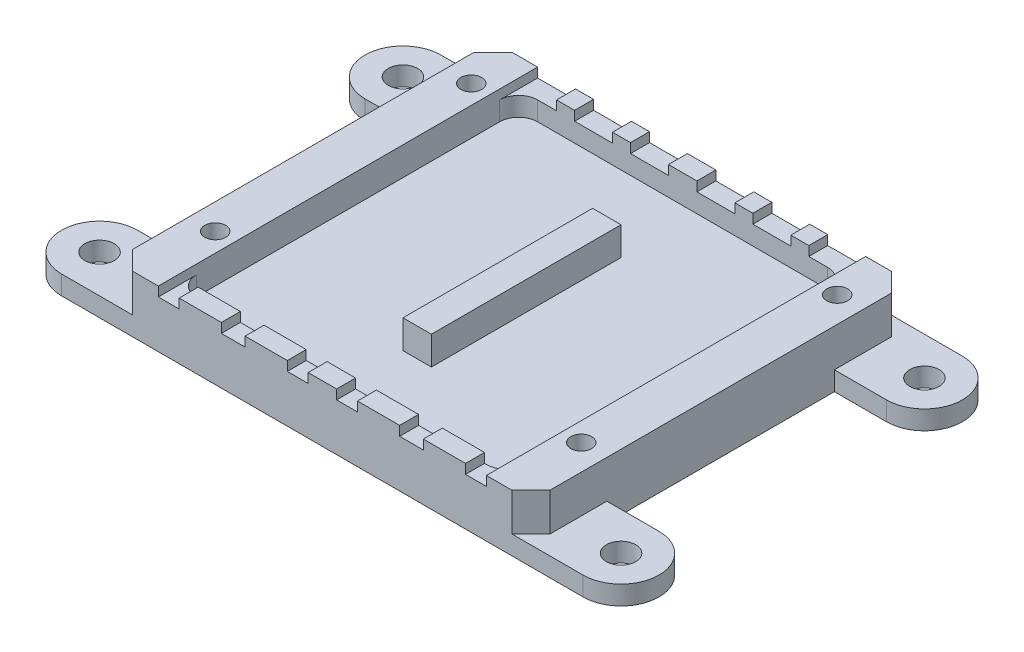
SolidWorks part; units mm, degrees
ref_plane "前视基准面" through (0, 0, 0) normal (0, 0, 1) x (1, 0, 0)
ref_plane "上视基准面" through (0, 0, 0) normal (0, 1, 0) x (1, 0, 0)
ref_plane "右视基准面" through (0, 0, 0) normal (1, 0, 0) x (0, 0, -1)
sketch "草图1" plane through (0, 0, 0) normal (0, 1, 0) x (1, 0, 0)
  line L0 (27.5, -20) -> (22, -20)
  line L2 (-22, -20) -> (-16, -20)
  line L3 (-16, 20) -> (16, 20)
  line L4 (-27.5, -12) -> (-22, -12)
  line L5 (-16, -20) -> (16, -20)
  line L6 (-22, 12) -> (-22, -12)
  line L7 (-22, 20) -> (22, -20) construction
  line L8 (-22, -20) -> (22, 20) construction
  line L9 (-22, 20) -> (-16, 20)
  line L10 (16, 20) -> (22, 20)
  line L11 (16, -20) -> (22, -20)
  line L12 (-27.5, 0) -> (-27.5, -16) construction
  line L13 (-27.5, -16) -> (27.5, -16) construction
  line L14 (27.5, -16) -> (27.5, 16) construction
  line L15 (27.5, 16) -> (-27.5, 16) construction
  line L16 (-27.5, 16) -> (-27.5, 0) construction
  line L17 (-22, -20) -> (-27.5, -20)
  line L18 (27.5, -12) -> (22, -12)
  line L19 (27.5, 12) -> (22, 12)
  line L20 (22, 20) -> (27.5, 20)
  line L21 (-22, 20) -> (-27.5, 20)
  line L22 (-27.5, 12) -> (-22, 12)
  line L23 (22, 12) -> (22, -12)
  circle A0 centre (-27.5, -16) radius 1.55
  circle A1 centre (-27.5, 16) radius 1.55
  circle A2 centre (27.5, 16) radius 1.55
  circle A3 centre (27.5, -16) radius 1.55
  arc A4 (27.5, -20) -> (27.5, -12) centre (27.5, -16) ccw
  arc A5 (-27.5, -12) -> (-27.5, -20) centre (-27.5, -16) ccw
  arc A6 (-27.5, 20) -> (-27.5, 12) centre (-27.5, 16) ccw
  arc A7 (27.5, 12) -> (27.5, 20) centre (27.5, 16) ccw
  point P5 (0, 0)
  point P31 (-22, 0)
  dimension "D1" = 40
  dimension "D2" = 44
extrude "凸台-拉伸1" add sketch "草图1" along normal blind 2
sketch "草图2" plane through (0, 2, 0) normal (0, 1, 0) x (1, 0, 0)
  line L0 (22, -20) -> (22, 20) construction
  line L1 (-27.5, -20) -> (27.5, -20) construction
  line L2 (-22, 20) -> (-22, -20) construction
  line L3 (27.5, 20) -> (-27.5, 20) construction
  line L4 (22, -20) -> (22, 20)
  line L5 (-22, -20) -> (22, -20)
  line L6 (-22, 20) -> (-22, -20)
  line L7 (22, 20) -> (-22, 20)
  point P12 (0, 0)
extrude "凸台-拉伸2" add sketch "草图2" along normal blind 4
sketch "草图3" plane through (0, 6, 0) normal (0, 1, 0) x (1, 0, 0)
  line L0 (-27.5525, 0) -> (27.6913, 0) construction
  line L1 (0, 25.4358) -> (0, -26.8932) construction
  line L2 (-1.5, 10) -> (-1.5, -10)
  line L3 (1.5, 10) -> (1.5, -10)
  line L15 (17.3, 18) -> (17.3, -18)
  line L16 (-17.3, 18) -> (-17.3, -18)
  line L20 (-22, -18) -> (22, -18)
  line L21 (-17.3, -18) -> (17.3, -18)
  line L22 (-17.3, 25.4358) -> (-17.3, -26.8932) construction
  line L23 (22, 18) -> (-22, 18)
  line L24 (17.3, 18) -> (-17.3, 18)
  line L25 (17.3, 25.4358) -> (17.3, -26.8932) construction
  line L26 (-1.5, -10) -> (1.5, -10)
  line L27 (-1.5, 10) -> (1.5, 10)
  line L28 (-27.5525, 10) -> (27.6913, 10) construction
  line L29 (-1.5, 25.4358) -> (-1.5, -26.8932) construction
  line L30 (-27.5525, -10) -> (27.6913, -10) construction
  line L31 (1.5, 25.4358) -> (1.5, -26.8932) construction
  dimension "D5" = 2
  dimension "D1" = 1.5
  dimension "D2" = 1.5
  dimension "D3" = 15.8
  dimension "D4" = 15.8
  dimension "D6" = 2
  dimension "D7" = 10
  dimension "D8" = 10
extrude "切除-拉伸1" cut sketch "草图3" against normal blind 3
sketch "草图4" plane through (0, 6, 0) normal (0, 1, 0) x (1, 0, 0)
  line L0 (-27.4831, 0) -> (27.2055, 0) construction
  line L1 (0, 25.5746) -> (0, -24.6723) construction
  line L2 (17.3, -18) -> (17.3, 18) construction
  line L3 (-17.3, 18) -> (-17.3, -18) construction
  line L4 (17.3, -20) -> (17.3, -18)
  line L5 (-17.3, 20) -> (-17.3, 18)
  line L6 (22, 20) -> (-22, 20) construction
  line L7 (-22, -20) -> (22, -20) construction
  line L8 (17.3, 20) -> (13.3, 20)
  line L9 (-17.3, -20) -> (-15.1, -20)
  line L10 (-13.3, 20) -> (-13.3, 18)
  line L11 (13.3, 18) -> (13.3, 20)
  line L12 (13.3, -18) -> (13.3, 20) construction
  line L13 (-13.3, 20) -> (-13.3, -18) construction
  line L14 (17.3, 18) -> (-17.3, 18) construction
  line L15 (17.3, 18) -> (13.3, 18)
  line L16 (-17.3, -18) -> (-17.3, -20)
  line L17 (-17.3, 20) -> (-17.3, -18) construction
  line L18 (17.3, 18) -> (17.3, 20)
  line L19 (17.3, -18) -> (17.3, 20) construction
  line L21 (-1.5, 10) -> (-1.5, -10) construction
  line L22 (1.5, -10) -> (1.5, 10) construction
  line L23 (-1.5, 20) -> (-1.5, 18)
  line L24 (5.5, 18) -> (5.5, 20)
  line L25 (-5.5, 20) -> (-5.5, 18)
  line L26 (1.5, -10) -> (1.5, 10) construction
  line L27 (-5.5, 20) -> (-5.5, -10) construction
  line L28 (-1.5, 20) -> (-5.5, 20)
  line L29 (-1.5, 18) -> (-5.5, 18)
  line L30 (1.5, 18) -> (1.5, 20)
  line L31 (-1.5, 10) -> (-1.5, -10) construction
  line L33 (-1.5, 20) -> (-1.5, -10) construction
  line L34 (1.5, -20) -> (3.7, -20)
  line L35 (1.5, -18) -> (3.7, -18)
  line L36 (-9.4, 25.5746) -> (-9.4, -24.6723) construction
  line L37 (9.4, 25.5746) -> (9.4, -24.6723) construction
  line L38 (7.4, 20) -> (7.4, 18)
  line L39 (11.4, 20) -> (11.4, 18)
  line L40 (-7.4, 20) -> (-7.4, 18)
  line L41 (-11.4, 20) -> (-11.4, 18)
  line L42 (-13.3, 20) -> (-17.3, 20)
  line L43 (-13.3, 18) -> (-17.3, 18)
  line L44 (-7.4, 20) -> (-11.4, 20)
  line L45 (-7.4, 18) -> (-11.4, 18)
  line L46 (5.5, 20) -> (1.5, 20)
  line L47 (5.5, 18) -> (1.5, 18)
  line L48 (11.4, 20) -> (7.4, 20)
  line L49 (11.4, 18) -> (7.4, 18)
  line L50 (-11.4, 25.5746) -> (-11.4, -24.6723) construction
  line L51 (-7.4, 25.5746) -> (-7.4, -24.6723) construction
  line L52 (7.4, 25.5746) -> (7.4, -24.6723) construction
  line L53 (11.4, 25.5746) -> (11.4, -24.6723) construction
  line L54 (-17.3, -18) -> (17.3, -18) construction
  line L55 (-17.3, -18) -> (-15.1, -18)
  line L56 (-15.1, -18) -> (-15.1, -20)
  line L57 (15.1, -20) -> (15.1, -18)
  line L58 (1.5, -18) -> (1.5, -20)
  line L59 (-1.5, -18) -> (-1.5, -20)
  line L60 (-3.7, -18) -> (-3.7, -20)
  line L61 (3.7, -18) -> (3.7, -20)
  line L62 (-10.65, -18) -> (-10.65, -20)
  line L63 (-8.15, -18) -> (-8.15, -20)
  line L64 (8.15, -18) -> (8.15, -20)
  line L65 (10.65, -18) -> (10.65, -20)
  line L66 (8.15, -18) -> (10.65, -18)
  line L67 (8.15, -20) -> (10.65, -20)
  line L68 (15.1, -18) -> (17.3, -18)
  line L69 (15.1, -20) -> (17.3, -20)
  line L70 (-3.7, -18) -> (-1.5, -18)
  line L71 (-3.7, -20) -> (-1.5, -20)
  line L72 (-10.65, -18) -> (-8.15, -18)
  line L73 (-10.65, -20) -> (-8.15, -20)
  line L74 (-10.65, 25.5746) -> (-10.65, -24.6723) construction
  line L75 (-8.15, 25.5746) -> (-8.15, -24.6723) construction
  line L76 (8.15, 25.5746) -> (8.15, -24.6723) construction
  line L77 (10.65, 25.5746) -> (10.65, -24.6723) construction
  dimension "D5" = 9.4
  dimension "D11" = 2.2
  dimension "D3" = 2
  dimension "D19" = 4
  dimension "D1" = 4
  dimension "D2" = 4
  dimension "D4" = 4
  dimension "D6" = 9.4
  dimension "D7" = 2
  dimension "D8" = 2
  dimension "D9" = 2
  dimension "D10" = 2
  dimension "D12" = 2.2
  dimension "D13" = 2.2
  dimension "D14" = 2.2
  dimension "D15" = 1.25
  dimension "D16" = 1.25
  dimension "D17" = 1.25
  dimension "D18" = 1.25
extrude "切除-拉伸2" cut sketch "草图4" against normal blind 1
fillet "圆角2" radius 2 4 edges at (17.3, 4, -18) (-17.3, 4, -18) (-17.3, 4, 18) (17.3, 4, 18)
sketch "草图5" plane through (0, 6, 0) normal (0, 1, 0) x (1, 0, 0)
  line L0 (-29.4032, 0) -> (28.1262, 0) construction
  line L1 (0, 28.1432) -> (0, -32.3448) construction
  line L8 (-22, 20) -> (-22, -20) construction
  line L9 (22, -20) -> (22, 20) construction
  circle A0 centre (19.3, 15) radius 1.1
  circle A1 centre (19.3, -12) radius 1.1
  circle A2 centre (-19.3, -12) radius 1.1
  circle A3 centre (-19.3, 15) radius 1.1
  dimension "D1" = 2.2
  dimension "D2" = 2.7
  dimension "D3" = 2.7
  dimension "D4" = 15
  dimension "D5" = 12
extrude "切除-拉伸3" cut sketch "草图5" against normal through all
sketch "草图6" plane through (0, 0, 0) normal (0, -1, 0) x (1, 0, 0)
  circle A0 centre (19.3, 12) radius 2
  circle A1 centre (-19.3, 12) radius 2
  circle A2 centre (-19.3, -15) radius 2
  circle A3 centre (19.3, -15) radius 2
  dimension "D1" = 4
extrude "切除-拉伸4" cut sketch "草图6" against normal blind 2.5
chamfer "Chamfer3" distance 2 angle 45 4 edges at (22, 4, 20) (-22, 4, 20) (-22, 4, -20) (22, 4, -20)
